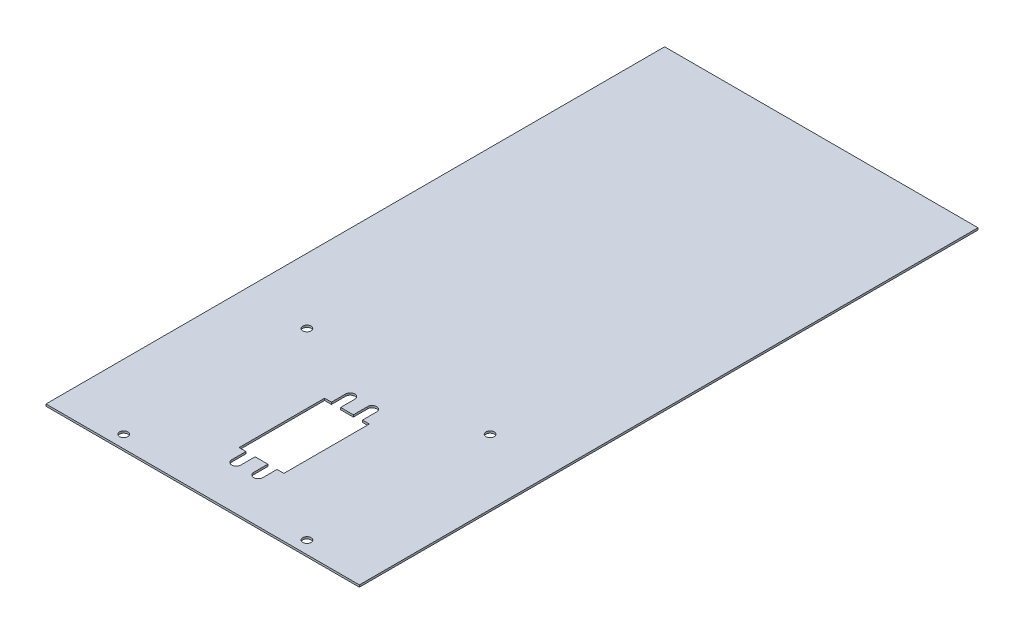
SolidWorks part; units mm, degrees
note: '?' marks a value the reader was unsure of.
ref_plane "Front Plane" through (0, 0, 0) normal (0, 0, 1) x (1, 0, 0)
ref_plane "Top Plane" through (0, 0, 0) normal (0, 1, 0) x (1, 0, 0)
ref_plane "Right Plane" through (0, 0, 0) normal (1, 0, 0) x (0, 0, -1)
sketch "Sketch1" plane through (0, 0, 0) normal (0, 1, 0) x (1, 0, 0)
  line L0 (0, 34.3446) -> (0, -28.4288) construction
  line L2 (-77, 34.3446) -> (77, 34.3446)
  line L3 (-77, 34.3446) -> (-77, -269.6554)
  line L4 (-77, -269.6554) -> (77, -269.6554)
  line L5 (77, 34.3446) -> (77, -269.6554)
  dimension "D1" = 154
  dimension "D2" = 304
base flange "Base-Flange1" sketch "Sketch1" thickness 1 reverse thickness direction no parameters "D1"=1
ref_axis "Axis1" through (0, 0, -34.3446) along (0, 0, 1)?
sketch "Sketch2" plane through (0, 0, 0) normal (0, 1, 0) x (1, 0, 0)
  line L0 (-77, -269.6554) -> (77, -269.6554) construction
  line L1 (-51.2, -269.6554) -> (51.2, -269.6554)
  line L2 (-51.2, -269.6554) -> (-51.2, -167.2554)
  line L3 (-51.2, -167.2554) -> (51.2, -167.2554)
  line L4 (51.2, -269.6554) -> (51.2, -167.2554)
  line L5 (-51.2, -269.6554) -> (51.2, -167.2554) construction
  line L6 (-51.2, -167.2554) -> (51.2, -269.6554) construction
  circle A0 centre (-45.02, -263.4754) radius 2.05
  circle A1 centre (-45.02, -173.4354) radius 2.05
  circle A2 centre (45.02, -173.4354) radius 2.05
  circle A3 centre (45.02, -263.4754) radius 2.05
  point P0 (0, -218.4554)
  dimension "D3" = 4.1
  dimension "D6" = 4.1
  dimension "D7" = 4.1
  dimension "D8" = 4.1
  dimension "D1" = 102.4
  dimension "D2" = 102.4
  dimension "D4" = 6.18
  dimension "D5" = 6.18
  dimension "D9" = 6.18
sketch "Sketch4" plane through (0, 0, 0) normal (0, 1, 0) x (1, 0, 0)
  line L0 (0, -269.6554) -> (0, -147.8165) construction
  line L1 (-77, -269.6554) -> (77, -269.6554) construction
  line L2 (-5.3842, -205.7554) -> (-5.3842, -191.7554) construction
  line L3 (11, -198.7554) -> (-11, -198.7554)
  line L4 (11, -198.7554) -> (11, -240.7554)
  line L5 (11, -240.7554) -> (-11, -240.7554)
  line L6 (-11, -198.7554) -> (-11, -240.7554)
  line L7 (11, -198.7554) -> (-11, -240.7554) construction
  line L8 (11, -240.7554) -> (-11, -198.7554) construction
  line L9 (-7.6342, -205.7554) -> (-7.6342, -191.7554)
  line L10 (-3.1342, -205.7554) -> (-3.1342, -191.7554)
  line L11 (0, -219.7554) -> (-39.7552, -219.7554) construction
  arc A0 (-7.6342, -205.7554) -> (-3.1342, -205.7554) centre (-5.3842, -205.7554) ccw
  arc A1 (-3.1342, -191.7554) -> (-7.6342, -191.7554) centre (-5.3842, -191.7554) ccw
  point P6 (0, -219.7554)
  point P13 (-5.3842, -198.7554)
  dimension "D1" = 28.9
  dimension "D2" = 42
  dimension "D3" = 22
  dimension "D4" = 4.5
  dimension "D5" = 14
ref_plane "Plane1" through (0, 0, 219.7554) normal (0, 0, -1) x (-1, 0, 0)
ref_plane "Plane2" through (0, 0, 0) normal (1, 0, 0) x (0, 0, -1)
extrude "Cut-Extrude3" cut sketch "Sketch4" against normal blind 10 contours A0 L9 L3 L6 L5 L4 L10
mirror "Mirror1" about plane through (0, 0, 0) normal (1, 0, 0) of "Cut-Extrude3"
mirror "Mirror2" about plane through (0, 0, 219.7554) normal (0, 0, -1) of "Mirror1", "Cut-Extrude3"
extrude "Cut-Extrude4" cut sketch "Sketch2" against normal blind 10 contours A3 | A2 | A1 | A0 normal cut yes
sketch "Bend-Lines1" plane through (0, 0, 0) normal (0, 1, 0) x (1, 0, 0)
sketch "Bounding-Box1" plane through (0, 0, 0) normal (0, 1, 0) x (1, 0, 0)
sheet metal parameters "Sheet-Metal(1)" thickness 1 parameters "D1"=1
flat pattern "Flat-Pattern(1)" [suppressed]
sketch "Bend-Lines2" plane through (0, 0, 0) normal (0, 1, 0) x (1, 0, 0)
sketch "Bounding-Box2" [suppressed] plane through (0, 0, 0) normal (0, 1, 0) x (1, 0, 0)
sheet metal parameters "Sheet-Metal(15)" thickness 1 parameters "D1"=1
flat pattern "Flat-Pattern(1)"
sketch "Bend-Lines2" plane through (0, 0, 0) normal (0, 1, 0) x (1, 0, 0)
sketch "Bounding-Box2" [suppressed] plane through (0, 0, 0) normal (0, 1, 0) x (1, 0, 0)
sheet metal parameters "Sheet-Metal(16)" thickness 1 parameters "D1"=1
flat pattern "Flat-Pattern(1)"
sketch "Bend-Lines2" plane through (0, 0, 0) normal (0, 1, 0) x (1, 0, 0)
sketch "Bounding-Box2" [suppressed] plane through (0, 0, 0) normal (0, 1, 0) x (1, 0, 0)
sheet metal parameters "Sheet-Metal(17)" thickness 1 parameters "D1"=1
flat pattern "Flat-Pattern(1)"
sketch "Bend-Lines2" plane through (0, 0, 0) normal (0, 1, 0) x (1, 0, 0)
sketch "Bounding-Box2" [suppressed] plane through (0, 0, 0) normal (0, 1, 0) x (1, 0, 0)
sheet metal parameters "Sheet-Metal(18)" thickness 1 parameters "D1"=1
flat pattern "Flat-Pattern(1)"
sketch "Bend-Lines2" plane through (0, 0, 0) normal (0, 1, 0) x (1, 0, 0)
sketch "Bounding-Box2" [suppressed] plane through (0, 0, 0) normal (0, 1, 0) x (1, 0, 0)
